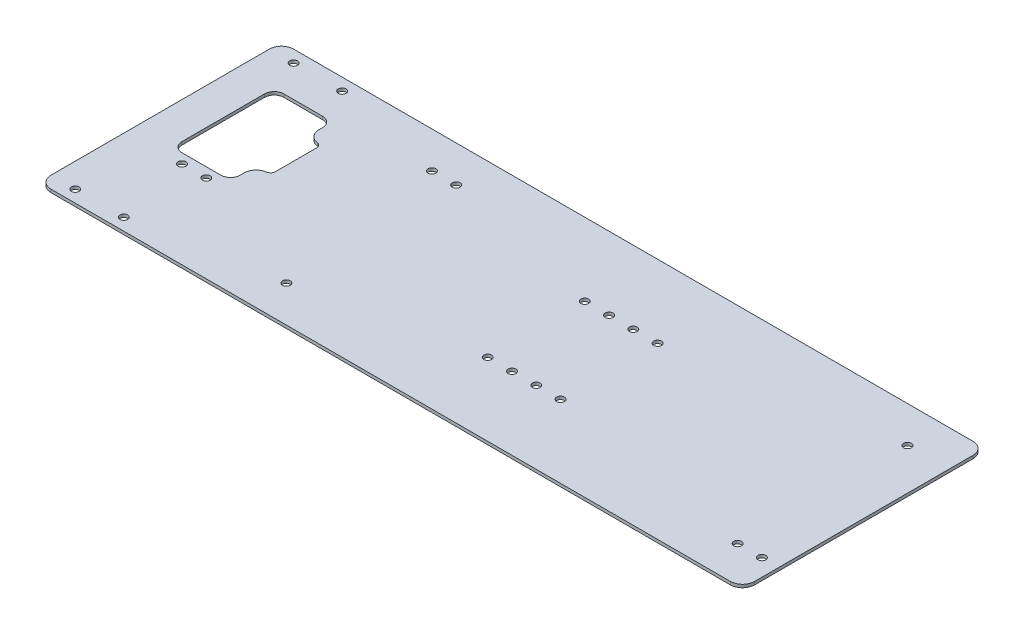
SolidWorks part; units mm, degrees
ref_plane "Front Plane" through (0, 0, 0) normal (0, 0, 1) x (1, 0, 0)
ref_plane "Top Plane" through (0, 0, 0) normal (0, 1, 0) x (1, 0, 0)
ref_plane "Right Plane" through (0, 0, 0) normal (1, 0, 0) x (0, 0, -1)
sketch "Sketch1" plane through (0, 0, 0) normal (0, 1, 0) x (1, 0, 0)
  line L0 (128.27, 0) -> (-128.27, 0) construction
  line L1 (184.15, 63.5) -> (-184.15, 63.5)
  line L2 (184.15, 63.5) -> (184.15, -63.5)
  line L3 (184.15, -63.5) -> (-184.15, -63.5)
  line L4 (-184.15, 63.5) -> (-184.15, -63.5)
  line L5 (184.15, 63.5) -> (-184.15, -63.5) construction
  line L6 (184.15, -63.5) -> (-184.15, 63.5) construction
  line L7 (-128.27, 0) -> (-128.27, 31.75) construction
  line L8 (-128.27, 31.75) -> (-134.62, 31.75) construction
  line L9 (-128.27, 6.35) -> (-134.62, 6.35) construction
  line L12 (-165.1, -12.7) -> (-165.1, 40.64)
  line L15 (-134.62, -12.7) -> (-165.1, -12.7)
  line L17 (-134.62, 40.64) -> (-165.1, 40.64)
  line L18 (0, 63.5) -> (0, -63.5) construction
  line L19 (-134.62, 40.64) -> (-134.62, -12.7)
  line L21 (-95.25, -45.0215) -> (-95.25, -32.3215) construction
  line L22 (-82.55, -45.0215) -> (-95.25, -45.0215) construction
  line L25 (128.27, 31.75) -> (128.27, 6.35) construction
  line L26 (-95.25, -32.3215) -> (-82.55, -32.3215) construction
  line L30 (-82.55, -32.3215) -> (-82.55, -45.0215) construction
  line L31 (184.15, -17.78) -> (154.94, -17.78) construction
  line L32 (146.05, 57.15) -> (184.15, 57.15) construction
  line L33 (154.94, -17.78) -> (142.24, -17.78) construction
  line L34 (146.05, -57.15) -> (184.15, -57.15) construction
  line L35 (-146.05, -57.15) -> (-184.15, -57.15) construction
  line L36 (-146.05, 57.15) -> (-184.15, 57.15) construction
  line L37 (-128.27, 0) -> (-128.27, 6.35) construction
  line L38 (-184.15, -17.78) -> (-154.94, -17.78) construction
  line L39 (-154.94, -17.78) -> (-142.24, -17.78) construction
  line L40 (-134.62, 27.305) -> (-127, 27.305)
  line L41 (-127, 27.305) -> (-127, 0.635)
  line L42 (-127, 0.635) -> (-134.62, 0.635)
  circle A4 centre (171.45, 31.75) radius 2.032 construction
  circle A5 centre (128.27, 31.75) radius 2.032 construction
  circle A6 centre (128.27, 6.35) radius 2.032 construction
  circle A7 centre (171.45, -3.81) radius 2.032 construction
  circle A8 centre (171.45, -57.15) radius 2.032
  circle A9 centre (146.05, -57.15) radius 2.032
  circle A10 centre (171.45, 57.15) radius 2.032
  circle A11 centre (146.05, 57.15) radius 2.032
  circle A12 centre (-146.05, -57.15) radius 2.032
  circle A13 centre (-171.45, -57.15) radius 2.032
  circle A14 centre (-146.05, 57.15) radius 2.032
  circle A15 centre (-171.45, 57.15) radius 2.032
  circle A16 centre (142.24, -17.78) radius 2.032 construction
  circle A17 centre (154.94, -17.78) radius 2.032 construction
  circle A18 centre (-154.94, -17.78) radius 2.032
  circle A19 centre (-142.24, -17.78) radius 2.032
  circle A20 centre (-95.25, -45.0215) radius 2.032
  circle A21 centre (-82.55, -45.0215) radius 2.032
  circle A22 centre (-95.25, -32.3215) radius 2.032
  circle A23 centre (-82.55, -32.3215) radius 2.032
  point P0 (0, 0)
  point P11 (-128.27, 0)
  point P13 (-134.62, 31.75)
  point P17 (-134.62, 6.35)
  point P37 (0, 0)
  point P50 (171.45, 57.15)
  point P51 (146.05, 57.15)
  point P56 (171.45, -57.15)
  point P57 (146.05, -57.15)
  point P84 (-130.81, 27.305)
  point P87 (130.81, 27.305)
  dimension "D5" = 13.335
  dimension "D18" = 4.064
  dimension "D1" = 368.3
  dimension "D2" = 127
  dimension "D3" = 128.27
  dimension "D4" = 25.4
  dimension "D7" = 6.35
  dimension "D8" = 30.48
  dimension "D9" = 53.34
  dimension "D10" = 8.89
  dimension "D11" = 19.05
  dimension "D14" = 12.7
  dimension "D15" = 38.1
  dimension "D16" = 12.7
  dimension "D17" = 38.1
  dimension "D19" = 31.75
  dimension "D20" = 6.35
  dimension "D21" = 6.35
  dimension "D22" = 5.08
  dimension "D23" = 29.21
  dimension "D24" = 12.7
  dimension "D25" = 88.9
  dimension "D26" = 12.7
  dimension "D27" = 7.62
  dimension "D28" = 26.67
  dimension "D29" = 13.335
  dimension "D30" = 18.4785
  dimension "D31" = 12.7
extrude "Boss-Extrude1" add sketch "Sketch1" along normal blind 1.5875 contours L1 L4 L3 L2 A18 A17 A16 A14 A12 A11 A10 A9 A8 L41 L42 L19 L15 L12 L17 L40 A13 A15 A19 | A20 | A22 | A23 | A21 | A9 | A8 | A10 | A11 region at (6.2259, 0, 0.5157)
sketch "Sketch2" [suppressed] plane through (0, 1.5875, 0) normal (0, 1, 0) x (1, 0, 0)
  line L0 (-69.85, 63.5) -> (-69.85, -63.5)
  line L1 (184.15, 63.5) -> (-184.15, 63.5) construction
  line L2 (184.15, -63.5) -> (-184.15, -63.5) construction
  circle A0 centre (-82.55, -45.0215) radius 2.032 construction
  circle M9 centre (146.05, 57.15) radius 2.032
  circle M10 centre (171.45, 57.15) radius 2.032
  circle M11 centre (146.05, -57.15) radius 2.032
  circle M12 centre (171.45, -57.15) radius 2.032
  line M13 (184.15, 63.5) -> (-184.15, 63.5)
  line M15 (-184.15, -63.5) -> (184.15, -63.5)
  line M16 (184.15, -63.5) -> (184.15, 63.5)
  dimension "D1" = 12.7
extrude "Cut-Extrude1" [suppressed] cut sketch "Sketch2" against normal through all flip side to cut contours L0 M13 M15 M16 M10 M12 M11 M9
fillet "Fillet1" radius 5.08 4 edges at (-134.62, 0.7937, 12.7) (-165.1, 0.7937, 12.7) (-165.1, 0.7937, -40.64) (-134.62, 0.7937, -40.64)
fillet "Fillet3" radius 6.35 4 edges at (184.15, 0.7937, 63.5) (184.15, 0.7937, -63.5) (-184.15, 0.7937, 63.5) (-184.15, 0.7937, -63.5)
fillet "Fillet4" radius 2.54 2 edges at (-127, 0.7937, -0.635) (-127, 0.7937, -27.305)
fillet "Fillet5" radius 6.35 2 edges at (-134.62, 0.7937, -0.635) (-134.62, 0.7937, -27.305)
fillet "Fillet6" [suppressed] radius 6.35
sketch "Sketch3" plane through (0, 1.5875, 0) normal (0, 1, 0) x (1, 0, 0)
  circle A0 centre (12.7, -25.4) radius 2.032 construction
  arc A1 (27.3352, -24.7804) -> (27.3352, -26.0196) centre (25.4, -25.4) ccw construction
  arc A2 (36.1648, -26.0196) -> (36.1648, -24.7804) centre (38.1, -25.4) ccw construction
  circle A3 centre (50.8, -25.4) radius 2.032 construction
  circle A4 centre (50.8, 25.4) radius 2.032 construction
  arc A5 (36.1648, 24.7804) -> (36.1648, 26.0196) centre (38.1, 25.4) ccw construction
  arc A6 (27.3352, 26.0196) -> (27.3352, 24.7804) centre (25.4, 25.4) ccw construction
  circle A7 centre (12.7, 25.4) radius 2.032 construction
  circle A8 centre (175.26, -44.45) radius 2.032 construction
  circle A9 centre (162.56, -44.45) radius 2.032 construction
  circle A10 centre (162.56, 44.45) radius 2.032 construction
  circle A11 centre (-73.66, 44.45) radius 2.032 construction
  circle A12 centre (-86.36, 44.45) radius 2.032 construction
  circle A13 centre (-73.66, -44.45) radius 2.032 construction
  circle A14 centre (12.7, -25.4) radius 2.032
  arc A15 (27.3352, -24.7804) -> (27.3352, -26.0196) centre (25.4, -25.4) ccw
  arc A16 (36.1648, -26.0196) -> (36.1648, -24.7804) centre (38.1, -25.4) ccw
  circle A17 centre (50.8, -25.4) radius 2.032
  circle A18 centre (50.8, 25.4) radius 2.032
  arc A19 (36.1648, 24.7804) -> (36.1648, 26.0196) centre (38.1, 25.4) ccw
  arc A20 (27.3352, 26.0196) -> (27.3352, 24.7804) centre (25.4, 25.4) ccw
  circle A21 centre (12.7, 25.4) radius 2.032
  circle A22 centre (175.26, -44.45) radius 2.032
  circle A23 centre (162.56, -44.45) radius 2.032
  circle A24 centre (162.56, 44.45) radius 2.032
  circle A25 centre (-73.66, 44.45) radius 2.032
  circle A26 centre (-86.36, 44.45) radius 2.032
  circle A27 centre (-73.66, -44.45) radius 2.032
  circle A28 centre (25.4, -25.4) radius 2.032
  circle A29 centre (38.1, -25.4) radius 2.032
  circle A30 centre (25.4, 25.4) radius 2.032
  circle A31 centre (38.1, 25.4) radius 2.032
extrude "Cut-Extrude5" cut sketch "Sketch3" against normal through all contours A26 | A24 | A15 A28 | A16 A29 | A20 A30 | A19 A31 | A27 | A25 | A21 | A14 | A17 | A18 | A23 | A22 region at (25.4, 1.5875, 25.4) region at (38.1, 1.5875, 25.4) region at (38.1, 1.5875, -25.4) region at (25.4, 1.5875, -25.4) region at (162.56, 1.5875, -44.45) region at (-86.36, 1.5875, -44.45)
equation "\".80.55in\"=0.55"
